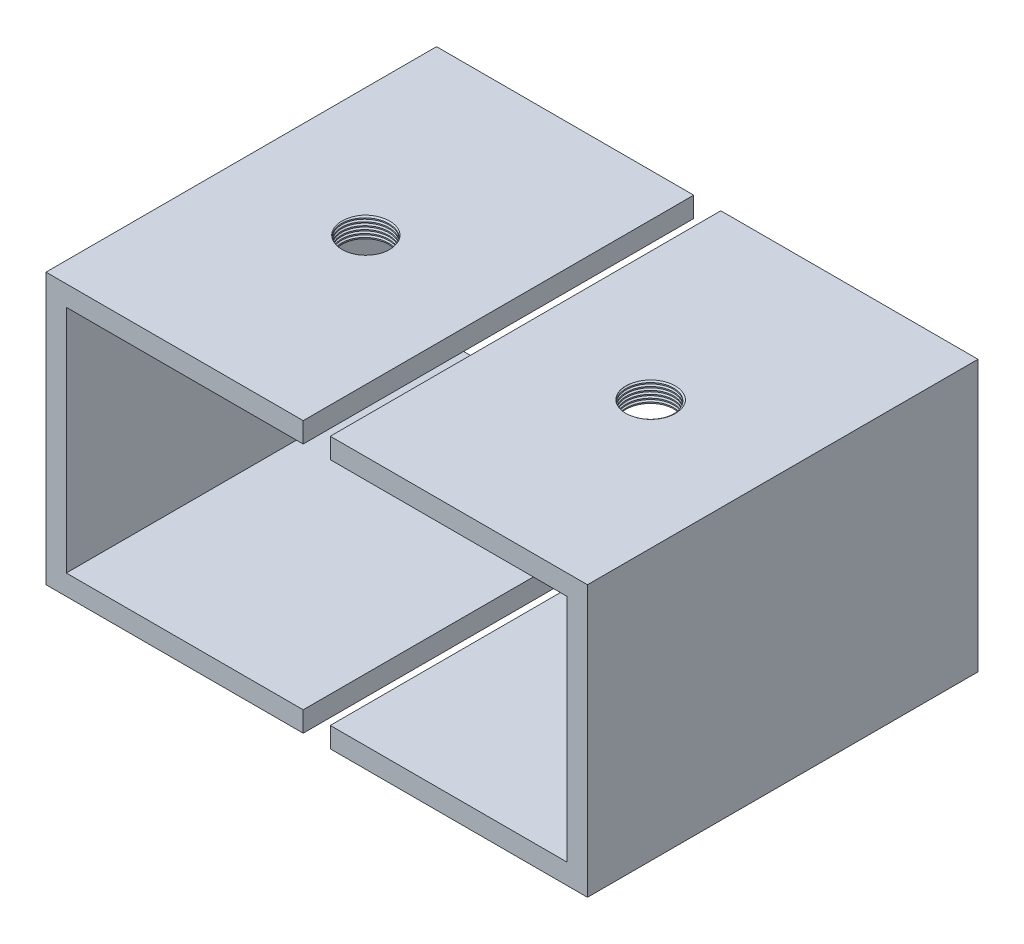
SolidWorks part; units mm, degrees
ref_plane "Front" through (0, 0, 0) normal (0, 0, 1) x (1, 0, 0)
ref_plane "Top" through (0, 0, 0) normal (0, 1, 0) x (1, 0, 0)
ref_plane "Right" through (0, 0, 0) normal (1, 0, 0) x (0, 0, -1)
sketch "Sketch1" plane through (0, 0, 0) normal (0, 0, 1) x (1, 0, 0)
  line L0 (185.259, -85.1295) -> (185.259, 84.8705)
  line L1 (185.259, 84.8705) -> (10.259, 84.8705)
  line L2 (-184.741, 84.8705) -> (-184.741, -85.1295)
  line L3 (-184.741, -85.1295) -> (-9.741, -85.1295)
  line L4 (200.259, -100.1295) -> (200.259, 99.8705)
  line L5 (200.259, 99.8705) -> (10.259, 99.8705)
  line L6 (-199.741, 99.8705) -> (-199.741, -100.1295)
  line L7 (-199.741, -100.1295) -> (-9.741, -100.1295)
  line L8 (-9.741, 84.8705) -> (-9.741, 99.8705)
  line L9 (10.259, 84.8705) -> (10.259, 99.8705)
  line L10 (-9.741, 99.8705) -> (-199.741, 99.8705)
  line L11 (-9.741, 84.8705) -> (-184.741, 84.8705)
  line L12 (-9.741, -100.1295) -> (-9.741, -85.1295)
  line L13 (10.259, 99.8705) -> (10.259, 84.8705)
  line L14 (10.259, -85.1295) -> (10.259, -100.1295)
  line L15 (-9.741, 84.8705) -> (-9.741, 99.8705)
  line L16 (10.259, -85.1295) -> (185.259, -85.1295)
  line L17 (10.259, -100.1295) -> (200.259, -100.1295)
extrude "Boss-Extrude1" add sketch "Sketch1" along normal blind 288.5 contours L7 L12 L3 L2 L11 L8 L10 L6 | L14 L17 L4 L5 L9 L1 L0 L16 region at (188.0177, -0.1295, 0) region at (-187.4996, -0.1295, 0)
sketch "Sketch2" plane through (0, 99.8705, 0) normal (0, 1, 0) x (1, 0, 0)
  line L0 (-104.741, -5.9382) -> (-104.741, -288.5) construction
  line L1 (-9.741, -288.5) -> (-199.741, -288.5) construction
  line L3 (-199.741, -288.5) -> (-199.741, 0) construction
  line L4 (0, 0) -> (0, -290.8396) construction
  circle A0 centre (-104.741, -147.2191) radius 17.5
  circle A1 centre (104.741, -147.2191) radius 17.5
  dimension "D2" = 35
  dimension "D1" = 95
extrude "Cut-Extrude1" cut sketch "Sketch2" against normal blind 24
sketch "Sketch3" plane through (0, 99.8705, 0) normal (0, 1, 0) x (1, 0, 0)
  circle A0 centre (-104.741, -147.2191) radius 17.5 construction
  circle A1 centre (-104.741, -147.2191) radius 17.5
curve "Helix/Spiral1" pitch 2.5 height 15 radius 17.5 centre (-104.741, 99.8705, 147.2191) axis (0, -1, 0) start towards (0, 0, 1)
ref_plane "Plane1" through (-117.1153, 99.8705, 134.8447) normal (0.7069, -0.0227, -0.7069) x (-0.7073, -0.0227, -0.7066)
sketch "Sketch4" plane through (-117.1153, 99.8705, 134.8447) normal (0.7069, -0.0227, -0.7069) x (-0.7073, -0.0227, -0.7066)
  line L1 (-0.7073, -1.225) -> (1.4145, 0)
  line L2 (1.4145, 0) -> (-0.7073, 1.225)
  line L3 (-0.7073, 1.225) -> (-0.7073, -1.225)
  circle A0 centre (0, 0) radius 0.7073 construction
  point P1 (0, 0)
  point P7 (0.3159, -0.0172)
  point P8 (0, 0)
  dimension "D1" = 2.45
sweep "Cut-Sweep1" cut profiles "Sketch4" path "Helix/Spiral1" align with end faces yes
mirror "Mirror4" about plane through (0, 0, 0) normal (1, 0, 0) of "Cut-Extrude1", "Cut-Sweep1"
